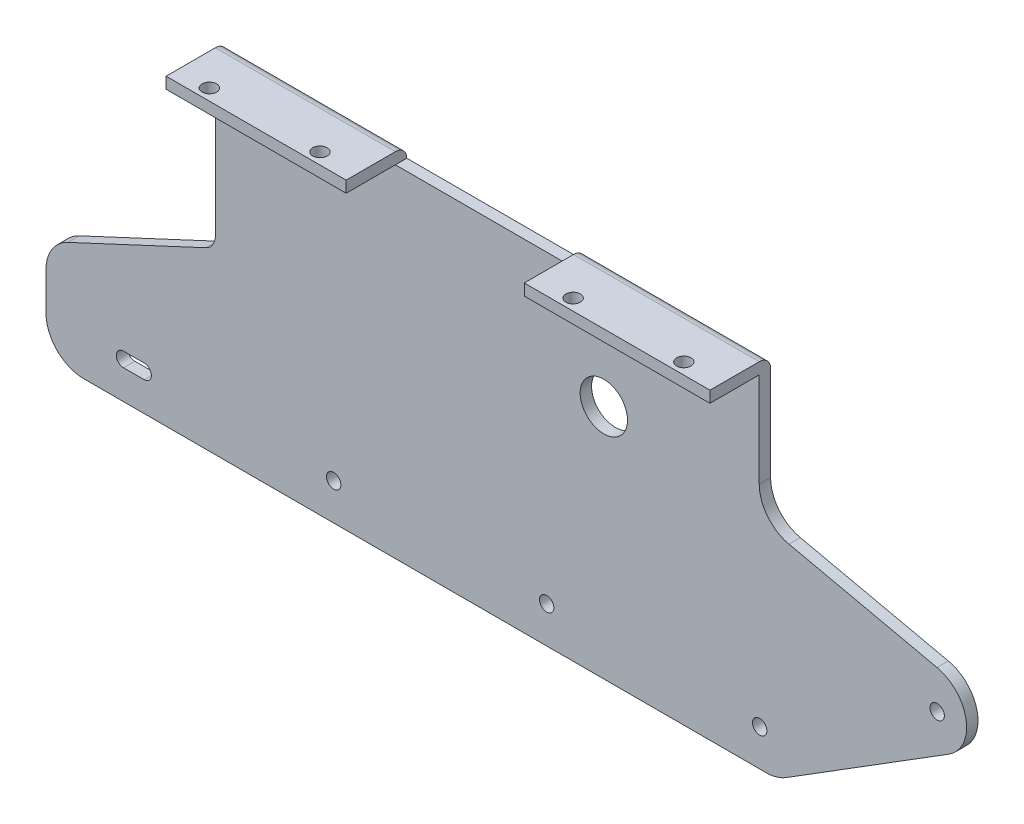
SolidWorks part; units mm, degrees
material "1060 Alloy"
ref_plane "Front Plane" through (0, 0, 0) normal (0, 0, 1) x (1, 0, 0)
ref_plane "Top Plane" through (0, 0, 0) normal (0, 1, 0) x (1, 0, 0)
ref_plane "Right Plane" through (0, 0, 0) normal (1, 0, 0) x (0, 0, -1)
sketch "Sketch1" plane through (0, 0, 0) normal (0, 0, 1) x (1, 0, 0)
  line L0 (0, 0) -> (143.5, 0)
  line L1 (143.5, 0) -> (143.5, -25)
  line L2 (151.3356, -34.763) -> (190.3874, -43.4205)
  line L3 (193.5222, -61.664) -> (150.6069, -88.4805)
  line L4 (145.3077, -90) -> (-34.6923, -90)
  line L5 (-44.6923, -80) -> (-44.6923, -70)
  line L6 (-38.9185, -60.9369) -> (-2.5276, -43.9676)
  line L7 (0, 0) -> (0, -40)
  arc A0 (-44.6923, -70) -> (-38.9185, -60.9369) centre (-34.6923, -70) cw
  arc A1 (143.5, -25) -> (151.3356, -34.763) centre (153.5, -25) ccw
  arc A2 (190.3874, -43.4205) -> (193.5222, -61.664) centre (188.223, -53.1835) cw
  arc A3 (145.3077, -90) -> (150.6069, -88.4805) centre (145.3077, -80) ccw
  arc A4 (-44.6923, -80) -> (-34.6923, -90) centre (-34.6923, -80) ccw
  arc A5 (-2.5276, -43.9676) -> (0, -40) centre (-4.3777, -40) ccw
  dimension "D6" = 10
  dimension "D7" = 10
  dimension "D10" = 10
  dimension "D11" = 40
  dimension "D12" = 10
  dimension "D15" = 10
  dimension "D1" = 143.5
  dimension "D2" = 25
  dimension "D3" = 40
  dimension "D4" = 90
  dimension "D5" = 12.5
  dimension "D8" = 180
  dimension "D9" = 32
  dimension "D13" = 10
  dimension "D14" = 25
extrude "Boss-Extrude1" add sketch "Sketch1" along normal blind 3
sketch "Sketch2" plane through (0, 0, 3) normal (0, 0, 1) x (1, 0, 0)
  line L0 (190.448, -53.5027) -> (198.218, -53.5027) construction
  line L1 (190.448, -53.5027) -> (190.3874, -43.4205) construction
  line L2 (190.448, -53.5027) -> (190.448, -63.585) construction
  line L3 (150.6069, -88.4805) -> (193.5222, -61.664) construction
  line L4 (143.6184, -80.35) -> (143.6184, -90) construction
  line L5 (-34.6923, -90) -> (145.3077, -90) construction
  line L6 (143.6184, -80.35) -> (163.6184, -80.35) construction
  line L7 (143.6184, -80.35) -> (87.4184, -80.35) construction
  line L8 (87.4184, -80.35) -> (31.2184, -80.35) construction
  line L9 (31.2184, -80.35) -> (-18.7816, -80.35) construction
  line L10 (-18.7816, -80.35) -> (-24.2316, -80.35) construction
  line L11 (-18.7816, -82.25) -> (-24.2316, -82.25)
  line L12 (-18.7816, -78.45) -> (-24.2316, -78.45)
  line L13 (102.5, -27.75) -> (0, -27.75) construction
  line L14 (0, 0) -> (0, -40) construction
  line L15 (143.5, 0) -> (0, 0) construction
  circle A0 centre (190.448, -53.5027) radius 1.9
  arc A1 (193.5222, -61.664) -> (190.3874, -43.4205) centre (188.223, -53.1835) ccw construction
  circle A2 centre (143.6184, -80.35) radius 1.9
  circle A3 centre (87.4184, -80.35) radius 1.9
  circle A4 centre (31.2184, -80.35) radius 1.9
  arc A5 (-18.7816, -82.25) -> (-18.7816, -78.45) centre (-18.7816, -80.35) ccw
  arc A6 (-24.2316, -78.45) -> (-24.2316, -82.25) centre (-24.2316, -80.35) ccw
  circle A7 centre (102.5, -27.75) radius 6.25
  point P22 (-21.5066, -80.35)
  dimension "D1" = 3.8
  dimension "D7" = 1.9
  dimension "D8" = 5.45
  dimension "D11" = 12.5
  dimension "D2" = 7.77
  dimension "D3" = 9.65
  dimension "D4" = 20
  dimension "D5" = 56.2
  dimension "D6" = 50
  dimension "D9" = 102.5
  dimension "D10" = 27.75
extrude "Cut-Extrude1" cut sketch "Sketch2" against normal through all contours A7 | A2 | A0 | A3 | A4 | L12 A6 L11 A5
sketch "Sketch3" plane through (143.5, 0, 0) normal (1, 0, 0) x (0, 0, -1)
  line L0 (0, 0) -> (-16, 0)
  line L1 (-3, 3) -> (-16, 3)
  line L2 (-16, 3) -> (-16, 0)
  line L3 (-3, 0) -> (0, 0)
  line L4 (-3, -25) -> (-3, 0) construction
  line L5 (-3, -25) -> (-3, 0)
  line L6 (0, -25) -> (0, 0) construction
  line L7 (0, -25) -> (0, 0)
  arc A2 (-3, 3) -> (0, 0) centre (-3, 0) cw
  line M10 (0, 0) -> (-3, 0)
  dimension "D1" = 3
  dimension "D2" = 16
extrude "Boss-Extrude3" add sketch "Sketch3" against normal up to surface (143.5 mm away) contours A2 L1 L2 L0 M10 region at (143.5, 1.4652, 8.3073) up to face at (0, -20, 1.5)
sketch "Sketch6" plane through (0, 3, 0) normal (0, 1, 0) x (1, 0, 0)
  line L0 (47.5, 0) -> (94.5, 0)
  line L1 (143.5, 0) -> (0, 0) construction
  line L2 (94.5, 0) -> (94.5, -16)
  line L3 (0, -16) -> (143.5, -16) construction
  line L4 (94.5, -16) -> (47.5, -16)
  line L5 (47.5, -16) -> (47.5, 0)
  line L6 (0, -16) -> (0, -3) construction
  line L7 (143.5, -3) -> (143.5, -16) construction
  dimension "D1" = 47.5
  dimension "D2" = 49
extrude "Cut-Extrude4" cut sketch "Sketch6" against normal up to vertex (3 mm away) up to point (143.5, 0, 3)
sketch "Sketch7" plane through (0, 3, 0) normal (0, 1, 0) x (1, 0, 0)
  line L0 (0, -13) -> (143.5, -13) construction
  line L1 (0, -16) -> (0, -3) construction
  line L2 (143.5, -3) -> (143.5, -16) construction
  line L3 (0, -16) -> (47.5, -16) construction
  line L4 (94.5, -16) -> (94.5, -3) construction
  line L5 (47.5, -3) -> (47.5, -16) construction
  circle A0 centre (133.6, -13) radius 1.9
  circle A1 centre (104.4, -13) radius 1.9
  circle A2 centre (37.6, -13) radius 1.9
  circle A3 centre (8.4, -13) radius 1.9
  dimension "D6" = 3.8
  dimension "D1" = 3
  dimension "D2" = 9.9
  dimension "D3" = 9.9
  dimension "D4" = 9.9
  dimension "D5" = 8.4
extrude "Cut-Extrude5" cut sketch "Sketch7" against normal through all
